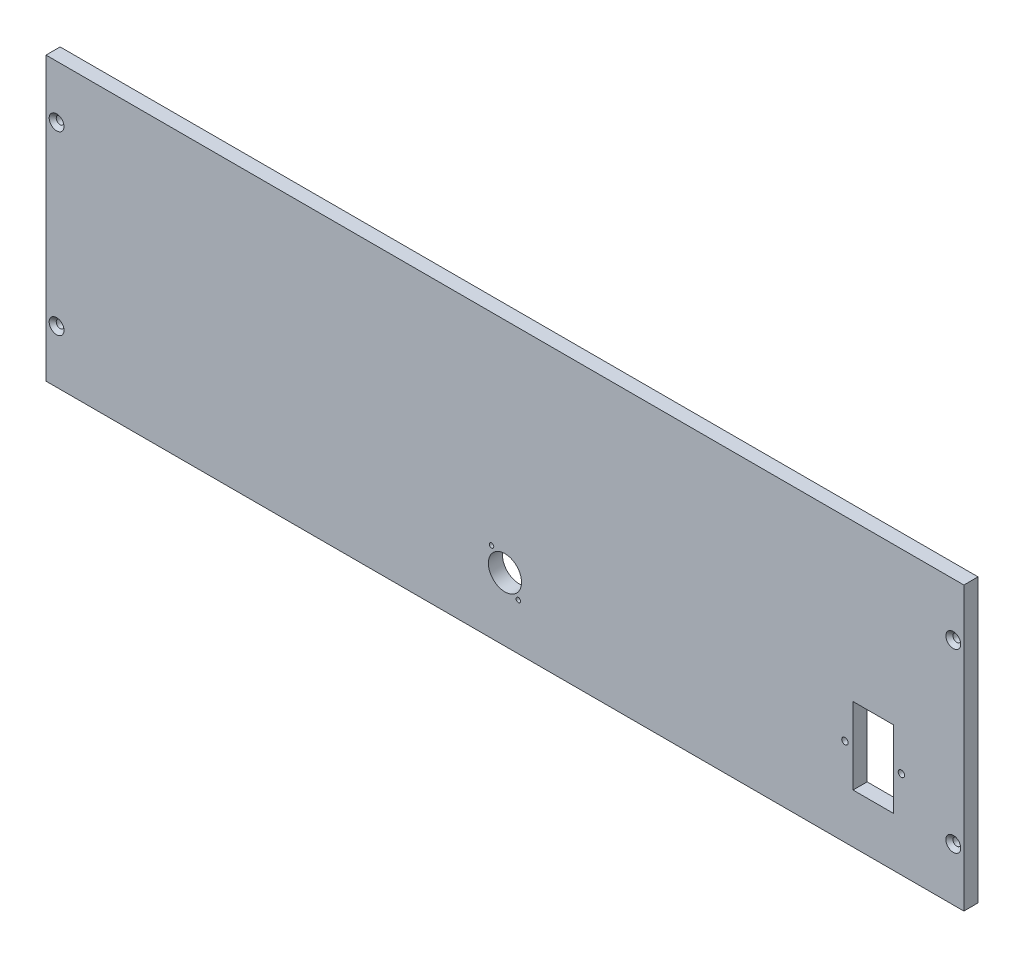
SolidWorks part; units mm, degrees
ref_plane "Plan de face" through (0, 0, 0) normal (0, 0, 1) x (1, 0, 0)
ref_plane "Plan de dessus" through (0, 0, 0) normal (0, 1, 0) x (1, 0, 0)
ref_plane "Plan de droite" through (0, 0, 0) normal (1, 0, 0) x (0, 0, -1)
sketch "Esquisse1" plane through (0, 0, 0) normal (0, 0, 1) x (1, 0, 0)
  line L1 (0, 0) -> (650, 0)
  line L2 (0, 0) -> (0, 200)
  line L3 (0, 200) -> (650, 200)
  line L4 (650, 0) -> (650, 200)
  dimension "D1" = 200
  dimension "D2" = 650
extrude "Boss.-Extru.1" add sketch "Esquisse1" along normal blind 10
sketch "Esquisse2" plane through (0, 0, 10) normal (0, 0, 1) x (1, 0, 0)
  line L0 (0, 200) -> (0, 0) construction
  line L1 (650, 200) -> (0, 200) construction
  line L2 (0, 0) -> (650, 0) construction
  line L3 (650, 0) -> (650, 200) construction
  circle A0 centre (7.5, 162.5) radius 2.75
  circle A1 centre (642.5, 162.5) radius 2.75
  circle A2 centre (7.5, 37.5) radius 2.75
  circle A3 centre (642.5, 37.5) radius 2.75
  dimension "D1" = 5.5
  dimension "D2" = 5.5
  dimension "D3" = 5.5
  dimension "D4" = 5.5
  dimension "D5" = 7.5
  dimension "D6" = 7.5
  dimension "D7" = 37.5
  dimension "D8" = 37.5
  dimension "D9" = 37.5
  dimension "D10" = 37.5
  dimension "D11" = 7.5
  dimension "D12" = 7.5
extrude "Enlèv. mat.-Extru.1" cut sketch "Esquisse2" against normal blind 10
chamfer "Chanfrein1" distance 2.5 angle 45 4 edges at (10.25, 162.5, 10) (10.25, 37.5, 10) (645.25, 37.5, 10) (645.25, 162.5, 10)
sketch "Esquisse3" plane through (0, 0, 10) normal (0, 0, 1) x (1, 0, 0)
  line L0 (0, 0) -> (650, 0) construction
  line L1 (334.5004, 33.0006) -> (325, 45)
  line L2 (325, 45) -> (315.4996, 56.9994)
  line L3 (325, 45) -> (265.8175, 45)
  line L4 (325, 45) -> (364.3682, 45)
  line L5 (650, 0) -> (650, 200) construction
  line L6 (571.5, 35) -> (600, 35)
  line L7 (571.5, 35) -> (571.5, 89.3)
  line L8 (571.5, 89.3) -> (600, 89.3)
  line L9 (600, 35) -> (600, 89.3)
  circle A0 centre (325, 45) radius 11.75
  circle A1 centre (315.4996, 56.9994) radius 1.6
  circle A2 centre (334.5004, 33.0006) radius 1.6
  circle A3 centre (565.75, 62.15) radius 2.25
  circle A4 centre (605.75, 62.15) radius 2.25
  point P4 (325, 0)
  point P19 (585.75, 89.3)
  point P20 (571.5, 62.15)
  point P21 (510.9417, 92.0447)
  dimension "D1" = 23.5
  dimension "D4" = 3.2
  dimension "D5" = 3.2
  dimension "D14" = 4.5
  dimension "D15" = 4.5
  dimension "D2" = 0
  dimension "D3" = 45
  dimension "D6" = 30.61
  dimension "D7" = 15.305
  dimension "D8" = 51.63
  dimension "D9" = 180
  dimension "D10" = 51.63
  dimension "D11" = 15.305
  dimension "D12" = 28.5
  dimension "D13" = 54.3
  dimension "D16" = 40
  dimension "D17" = 20
  dimension "D18" = 0
  dimension "D19" = 35
  dimension "D20" = 50
  dimension "D21" = 20
extrude "Enlèv. mat.-Extru.2" cut sketch "Esquisse3" against normal blind 10 contours L3 A0 L1 | L4 A0 L2 | L1 A0 L4 | L2 A0 L3 | A1 | A2 | L6 L9 L8 L7 | A3 | A4 region at (314.1, 57.6764, 10) region at (322.2589, 39.3335, 10) region at (331.8154, 41.7031, 10) region at (335.1774, 34.4002, 10) region at (318.1846, 48.2969, 10) region at (327.7411, 50.6665, 10) region at (585.75, 62.15, 10)
